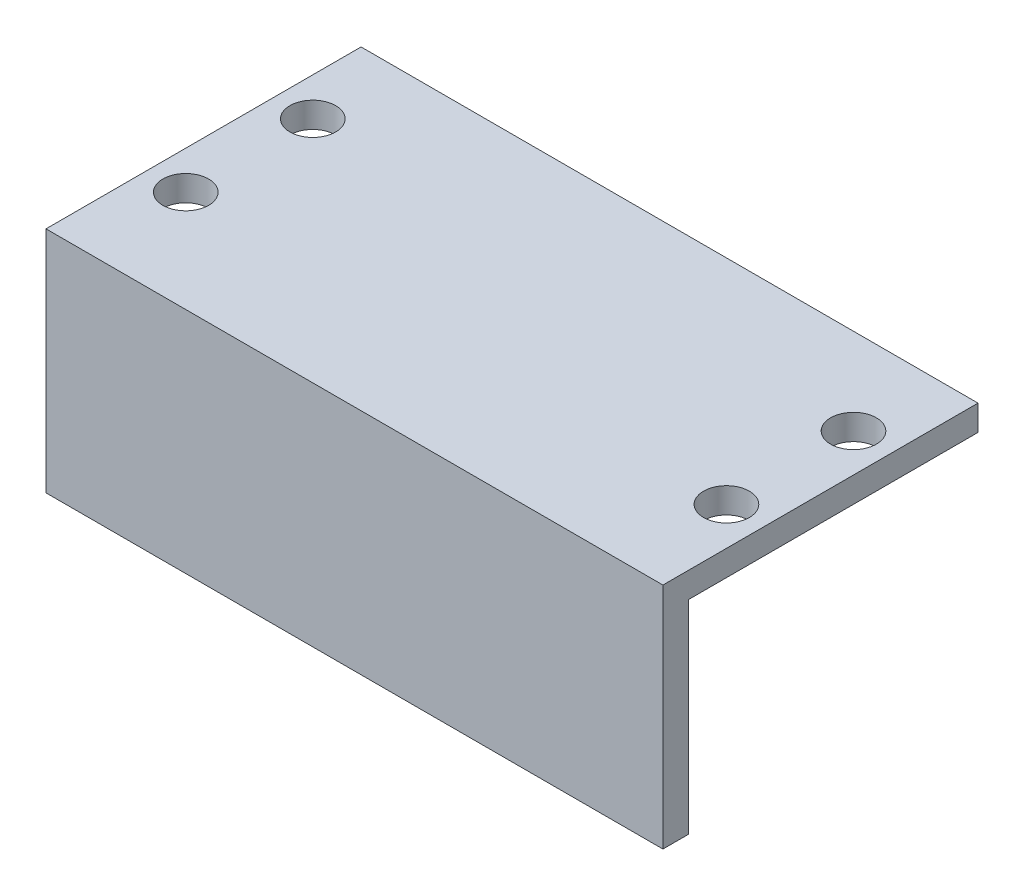
SolidWorks part; units mm, degrees
ref_plane "Front Plane" through (0, 0, 0) normal (0, 0, 1) x (1, 0, 0)
ref_plane "Top Plane" through (0, 0, 0) normal (0, 1, 0) x (1, 0, 0)
ref_plane "Right Plane" through (0, 0, 0) normal (1, 0, 0) x (0, 0, -1)
sketch "Sketch1" plane through (0, 0, 0) normal (0, 1, 0) x (1, 0, 0)
  line L0 (12.14, 11.4) -> (12.14, 0) construction
  line L1 (0, 0) -> (24.28, 0)
  line L2 (0, 0) -> (0, 11.4)
  line L3 (0, 11.4) -> (24.28, 11.4)
  line L4 (24.28, 0) -> (24.28, 11.4)
  line L6 (0, 0) -> (24.28, 0)
  line L7 (0, 0) -> (0, -1)
  line L8 (0, -1) -> (24.28, -1)
  line L9 (24.28, 0) -> (24.28, -1)
  circle A0 centre (1.5, 3) radius 0.9
  circle A1 centre (1.5, 8) radius 0.9
  circle A2 centre (22.78, 8) radius 0.9
  circle A3 centre (22.78, 3) radius 0.9
  dimension "D3" = 1.8
  dimension "D4" = 1.8
  dimension "D1" = 11.4
  dimension "D2" = 24.28
  dimension "D5" = 3
  dimension "D6" = 5
  dimension "D7" = 1.5
  dimension "D8" = 1
extrude "Boss-Extrude1" add sketch "Sketch1" along normal blind 1 contours L0 L3 L2 L1 A1 A0 | L3 L0 L6 L4 A3 A2 region at (18.0355, 0, -5.7076) region at (6.2445, 0, -5.7076)
extrude "Boss-Extrude2" add sketch "Sketch1<3>" along normal blind 1 and the other way blind 8 contours L9 L6 L1 L7 L8 region at (12.14, 0, 0.5)
sketch "Sketch1<3>" plane through (0, 0, 0) normal (0, 1, 0) x (1, 0, 0) same geometry as "Sketch1"
